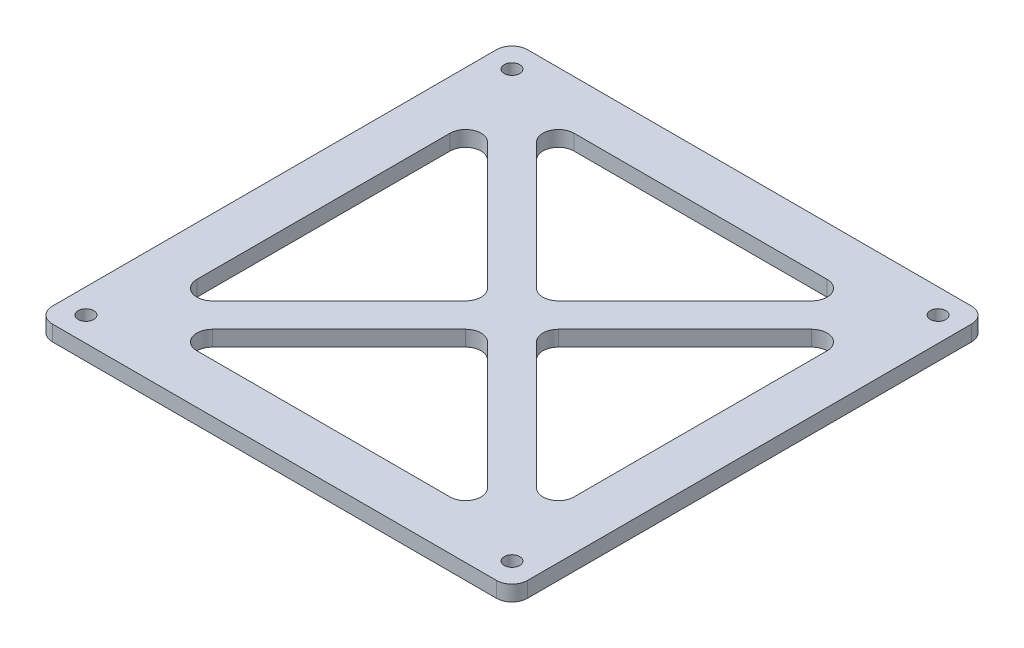
SolidWorks part; units mm, degrees
ref_plane "前基準面" through (0, 0, 0) normal (0, 0, 1) x (1, 0, 0)
ref_plane "上基準面" through (0, 0, 0) normal (0, 1, 0) x (1, 0, 0)
ref_plane "右基準面" through (0, 0, 0) normal (1, 0, 0) x (0, 0, -1)
sketch "草圖1" plane through (0, 0, 0) normal (0, 1, 0) x (1, 0, 0)
  line L0 (-41.25, 41.25) -> (41.25, 41.25) construction
  line L1 (-46, 46) -> (46, 46)
  line L2 (-46, 46) -> (-46, -46)
  line L3 (-46, -46) -> (46, -46)
  line L4 (46, 46) -> (46, -46)
  line L5 (-46, 46) -> (46, -46) construction
  line L6 (-46, -46) -> (46, 46) construction
  line L7 (-41.25, 41.25) -> (-41.25, -41.25) construction
  line L8 (-41.25, 41.25) -> (-41.25, 46) construction
  line L9 (-41.25, 41.25) -> (-46, 41.25) construction
  circle A0 centre (-41.25, 41.25) radius 1.5
  circle A1 centre (41.25, 41.25) radius 1.5
  circle A2 centre (41.25, -41.25) radius 1.5
  circle A3 centre (-41.25, -41.25) radius 1.5
  point P0 (0, 0)
  dimension "D7" = 3
  dimension "D1" = 92
  dimension "D2" = 92
  dimension "D5" = 82.5
  dimension "D6" = 82.5
  dimension "D8" = 4.75
  dimension "D3" = 2
  dimension "D4" = 2
extrude "填料-伸長1" add sketch "草圖1" along normal blind 3
sketch "草圖2" plane through (0, 3, 0) normal (0, 1, 0) x (1, 0, 0)
  line L0 (0, 0) -> (55.2066, 0) construction
  line L1 (55.2066, 0) -> (-60.768, 0) construction
  line L2 (0, 0) -> (0, 56.6444) construction
  line L3 (0, 56.6444) -> (0, -55.3423) construction
  line L5 (-36.5, 36.5) -> (36.5, 36.5)
  line L6 (-36.5, 36.5) -> (-36.5, -36.5)
  line L7 (-36.5, -36.5) -> (36.5, -36.5)
  line L8 (36.5, 36.5) -> (36.5, -36.5)
  line L9 (-36.5, 36.5) -> (36.5, -36.5) construction
  line L10 (-36.5, -36.5) -> (36.5, 36.5) construction
  dimension "D1" = 73
  dimension "D2" = 73
sketch "草圖3" plane through (0, 3, 0) normal (0, 1, 0) x (1, 0, 0)
  line L0 (-36.5, 31.75) -> (-4.75, 0)
  line L1 (-36.5, 36.5) -> (-36.5, -36.5) construction
  line L2 (55.2066, 0) -> (-60.768, 0) construction
  line L3 (-4.75, 0) -> (-36.5, -31.75)
  line L4 (-36.5, -31.75) -> (-36.5, 31.75)
  line L5 (-36.5, 36.5) -> (36.5, -36.5) construction
  line L6 (-36.5, -36.5) -> (36.5, 36.5) construction
  line L7 (-31.75, 36.5) -> (31.75, 36.5)
  line L8 (31.75, 36.5) -> (0, 4.75)
  line L9 (0, 4.75) -> (-31.75, 36.5)
  line L10 (36.5, 31.75) -> (36.5, -31.75)
  line L11 (36.5, -31.75) -> (4.75, 0)
  line L12 (4.75, 0) -> (36.5, 31.75)
  line L13 (31.75, -36.5) -> (-31.75, -36.5)
  line L14 (-31.75, -36.5) -> (0, -4.75)
  line L15 (0, -4.75) -> (31.75, -36.5)
  point P25 (0, 0)
  dimension "D1" = 4.75
  dimension "D2" = 4
extrude "除料-伸長1" cut sketch "草圖3" against normal through all contours L4 L3 L0 | L9 L8 L7 | L12 L11 L10 | L15 L14 L13 region at (-25.9167, 3, 0) region at (0, 3, -25.9167) region at (25.9167, 3, 0) region at (0, 3, 25.9167)
fillet "圓角1" radius 3 16 edges at (36.5, 1.5, 31.75) (4.75, 1.5, 0) (36.5, 1.5, -31.75) (-31.75, 1.5, -36.5) (31.75, 1.5, -36.5) (0, 1.5, -4.75) (-31.75, 1.5, 36.5) (31.75, 1.5, 36.5) (0, 1.5, 4.75) (-36.5, 1.5, 31.75) (-4.75, 1.5, 0) (-36.5, 1.5, -31.75) (-46, 1.5, 46) (46, 1.5, 46) (46, 1.5, -46) (-46, 1.5, -46)
